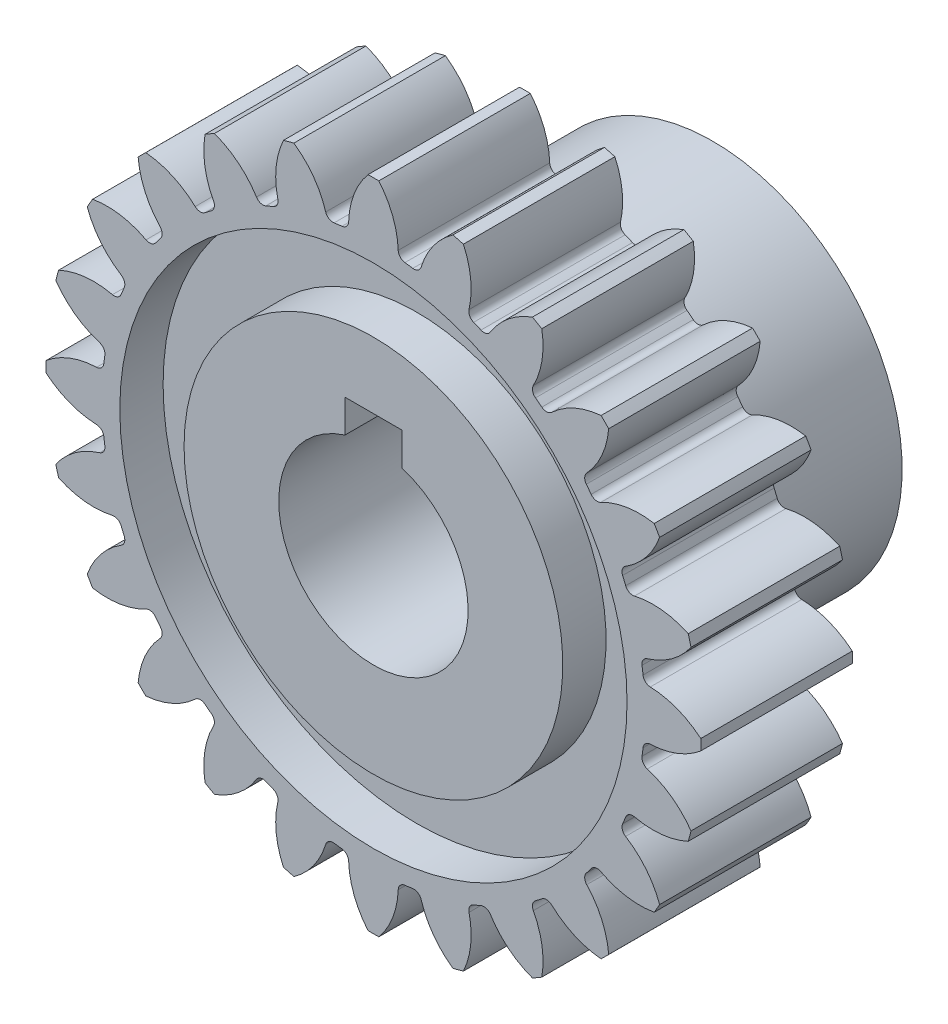
SolidWorks part; units mm, degrees
ref_plane "Front Plane" through (0, 0, 0) normal (0, 0, 1) x (1, 0, 0)
ref_plane "Top Plane" through (0, 0, 0) normal (0, 1, 0) x (1, 0, 0)
ref_plane "Right Plane" through (0, 0, 0) normal (1, 0, 0) x (0, 0, -1)
sketch "Sketch1" plane through (0, 0, 0) normal (1, 0, 0) x (0, 0, -1)
  line L0 (-7.112, 0) -> (-7.112, 13.7223)
  line L1 (-7.112, 13.7223) -> (-0.762, 13.7223)
  line L2 (-0.762, 13.7223) -> (-0.762, 7.9375)
  line L3 (-0.762, 7.9375) -> (7.112, 7.9375)
  line L4 (7.112, 7.9375) -> (7.112, 0)
  line L5 (7.112, 0) -> (-7.112, 0) construction
  line L6 (-7.112, 3.175) -> (7.112, 3.175)
  point P9 (-7.112, 10.6299)
  dimension "OD" = 27.4447
  dimension "Face Width" = 6.35
  dimension "Hub Width" = 7.874
  dimension "Hub Diameter" = 15.875
  dimension "For Shaft Diameter" = 6.35
  dimension "Overall Width" = 14.224
  dimension "Under Cut Diameter" = 21.2598
sketch "Sketch2" plane through (0, 0, 0) normal (0, 0, 1) x (1, 0, 0)
  line L0 (-1.3313, 11.2989) -> (-0.4492, 13.7223)
  line L1 (-0.4492, 13.7223) -> (0.4492, 13.7223)
  line L2 (0.4492, 13.7223) -> (1.3313, 11.2989)
  line L3 (0, 13.7223) -> (0, 0) construction
  line L4 (0, 0) -> (-1.7911, 13.605) construction
  line L5 (0, 0) -> (1.7911, 13.605) construction
  line L6 (-4.2103, 10.5694) -> (-3.9855, 13.1385)
  line L7 (-3.9855, 13.1385) -> (-3.1177, 13.371)
  line L8 (-3.1177, 13.371) -> (-1.6385, 11.2585)
  line L9 (-3.5516, 13.2548) -> (0, 0) construction
  line L11 (-0.4492, 13.7223) -> (0, 13.7223) construction
  line L12 (-0.8312, 12.6728) -> (0.8312, 12.6728) construction
  circle A0 centre (0, 0) radius 12.7 construction
  circle A2 centre (0, 0) radius 13.7223
  circle A3 centre (0, 0) radius 11.3771
  arc A5 (-0.2246, 13.7223) -> (-1.0378, 11.3296) centre (2.4404, 11.482) ccw
  arc A6 (1.0378, 11.3296) -> (0.2246, 13.7223) centre (-2.4404, 11.482) ccw
  arc A7 (-1.9298, 11.2122) -> (-3.3347, 13.3129) centre (-5.329, 10.4591) ccw
  arc A8 (-0.8312, 12.6728) -> (0.8312, 12.6728) centre (0, 0) cw
  point P3 (0, 12.7)
  point P5 (3.287, 12.2673)
  point P6 (-10.9985, 6.35)
  point P9 (6.35, 10.9985)
  point P10 (8.9803, 8.9803)
  point P11 (10.9985, 6.35)
  point P12 (12.2673, 3.287)
  point P13 (12.7, 0)
  point P14 (12.2673, -3.287)
  point P15 (10.9985, -6.35)
  point P16 (8.9803, -8.9803)
  point P17 (6.35, -10.9985)
  point P18 (3.287, -12.2673)
  point P19 (0, -12.7)
  point P20 (-3.287, -12.2673)
  point P21 (-6.35, -10.9985)
  point P22 (-8.9803, -8.9803)
  point P23 (-10.9985, -6.35)
  point P24 (-12.2673, -3.287)
  point P25 (-12.7, 0)
  point P26 (-12.2673, 3.287)
  point P27 (-8.9803, 8.9803)
  point P28 (-6.35, 10.9985)
  point P29 (-3.287, 12.2673)
  point P31 (0, 0)
  dimension "Gear Pitch Diameter" = 25.4
  dimension "Pressure Angle" = 20
  dimension "Addendum" = 1.0223
  dimension "Dedendum" = 1.3229
  dimension "D1" = 15
  dimension "D2" = 1.6624
  dimension "Number of Teeth" = 24
sketch "Sketch3" plane through (0, 0, 0) normal (1, 0, 0) x (0, 0, -1)
  line L0 (-7.112, 13.7223) -> (-0.762, 13.7223) construction
  line L1 (7.112, 7.9375) -> (7.112, 0) construction
  line L2 (-0.762, 7.9375) -> (7.112, 7.9375) construction
  line L3 (-0.762, 13.7223) -> (-0.762, 7.9375) construction
  line L4 (-7.112, 0) -> (-7.112, 13.7223) construction
  line L5 (-7.112, 3.175) -> (7.112, 3.175) construction
  line L6 (-7.112, 13.7223) -> (-0.762, 13.7223)
  line L7 (7.112, 7.9375) -> (7.112, 3.175)
  line L8 (-7.112, 7.9375) -> (-5.2977, 7.9375)
  line L9 (-0.762, 13.7223) -> (-0.762, 10.6299)
  line L10 (-7.112, 3.175) -> (-7.112, 7.9375)
  line L11 (-7.112, 3.175) -> (7.112, 3.175)
  line L12 (-7.112, 10.6299) -> (-5.2977, 10.6299)
  line L13 (-5.2977, 10.6299) -> (-5.2977, 7.9375)
  line L14 (-0.762, 10.6299) -> (-2.5763, 10.6299)
  line L15 (-2.5763, 10.6299) -> (-2.5763, 7.9375)
  line L16 (-2.5763, 7.9375) -> (7.112, 7.9375)
  line L17 (-7.112, 10.6299) -> (-7.112, 13.7223)
  dimension "D1" = 1.8143
revolve "Revolve1" add sketch "Sketch3" angle 360 about L5
sketch "Sketch4" plane through (0, 0, 7.112) normal (0, 0, 1) x (1, 0, 0)
  arc A1 (-0.2246, 13.7223) -> (-1.0378, 11.3296) centre (2.4404, 11.482) ccw construction
  arc A2 (-1.9298, 11.2122) -> (-3.3347, 13.3129) centre (-5.329, 10.4591) ccw construction
  arc A3 (-0.2262, 13.7205) -> (-1.039, 11.6045) centre (2.4404, 11.482) ccw
  arc A4 (-1.9998, 11.478) -> (-3.3327, 13.3115) centre (-5.329, 10.4591) ccw
  circle A5 centre (0, 0) radius 13.7223 construction
  arc A6 (-0.2262, 13.7205) -> (-3.3327, 13.3115) centre (0, 0) ccw
  circle A7 centre (0, 0) radius 11.3771 construction
  arc A8 (-1.3195, 11.3003) -> (-1.6502, 11.2568) centre (0, 0) ccw
  arc A9 (-1.9998, 11.478) -> (-1.6502, 11.2568) centre (-1.6962, 11.5709) ccw
  arc A10 (-1.3195, 11.3003) -> (-1.039, 11.6045) centre (-1.3563, 11.6157) ccw
  dimension "D1" = 0.3175
extrude "Cut-Extrude1" cut sketch "Sketch4" against normal through all both and the other way through all
pattern_circular "CirPattern1" count 24 over 360 about axis through (0, 0, -7.112) along (0, 0, -1) of "Cut-Extrude1"
sketch "Sketch5" plane through (0, 0, -7.112) normal (0, 0, -1) x (-1, 0, 0)
  line L1 (-1.1906, 5.1594) -> (1.1906, 5.1594)
  line L2 (-1.1906, 5.1594) -> (-1.1906, 2.7781)
  line L3 (-1.1906, 2.7781) -> (1.1906, 2.7781)
  line L4 (1.1906, 5.1594) -> (1.1906, 2.7781)
  line L5 (-1.1906, 5.1594) -> (1.1906, 2.7781) construction
  line L6 (-1.1906, 2.7781) -> (1.1906, 5.1594) construction
  circle A0 centre (0, 0) radius 3.9688
  point P3 (0, 3.9687)
  circle M4 centre (0, 0) radius 3.175
  dimension "D1" = 7.9375
  dimension "D2" = 2.3813
extrude "Cut-Extrude2" cut sketch "Sketch5" against normal through all contours L2 A0 L4 M4 | L4 A0 L2 M4 | A0 L4 L1 L2 region at (0, 4.5327, -7.112) region at (0, 3.5026, -7.112) region at (1.3016, 3.3646, -7.112)
equation "\"Dedendum@Sketch2\" = 1.25 /  ( \"Number of Teeth@Sketch2\" / \"Gear Pitch Diameter@Sketch2\" ) "
equation "\"D1@Sketch2\"=360/\"Number of Teeth@Sketch2\""
equation "\"D1@Sketch4\"=.3/(\"Number of Teeth@Sketch2\"/\"Gear Pitch Diameter@Sketch2\")"
equation "\"D1@CirPattern1\"=\"Number of Teeth@Sketch2\""
equation "\"D2@Sketch2\"=1.5708/(\"Number of Teeth@Sketch2\"/\"Gear Pitch Diameter@Sketch2\")"
equation "\"D1@Sketch3\"=\"Face Width@Sketch1\"/3.5"
